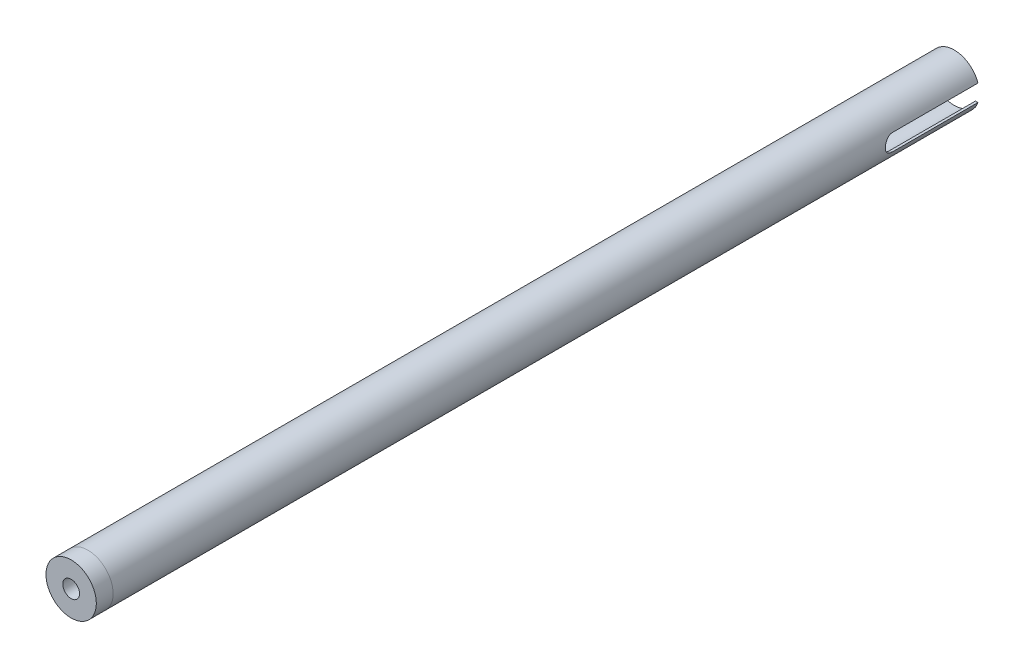
SolidWorks part; units mm, degrees
material "AISI 4130 Steel, normalized at 870C"
ref_plane "Front Plane" through (0, 0, 0) normal (0, 0, 1) x (1, 0, 0)
ref_plane "Top Plane" through (0, 0, 0) normal (0, 1, 0) x (1, 0, 0)
ref_plane "Right Plane" through (0, 0, 0) normal (1, 0, 0) x (0, 0, -1)
sketch "Axis" plane through (0, 0, 0) normal (0, 1, 0) x (1, 0, 0)
  line L0 (0, 0) -> (0, 333.8909) construction
  line L1 (0, 0) -> (0, -21.59) construction
  line L2 (0, 333.8909) -> (-9.525, 333.8909) construction
  line L3 (0, 368.3926) -> (-10.3187, 331.0158) construction
  dimension "D1" = 21.59
  dimension "D2" = 9.525
sketch "Sketch1" plane through (0, 0, 0) normal (0, 0, 1) x (1, 0, 0)
  line L0 (-9.525, 0) -> (9.525, 0) construction
  line L1 (-8.9803, 3.175) -> (8.9803, 3.175)
  line L2 (-8.9803, -3.175) -> (8.9803, -3.175)
  circle A0 centre (0, 0) radius 9.525
  circle A1 centre (0, 0) radius 8.636
  circle A2 centre (0, 0) radius 3.175
  dimension "D1" = 19.05
  dimension "D3" = 6.35
  dimension "D2" = 0.889
  dimension "D4" = 6.35
extrude "Threaded insert 1-1" add sketch "Sketch1" against normal blind 6.35 contours A2 L1 A1 | A1 L1 A0 | A2 L0 A1 L1 | A1 L0 A0 L1 | L0 A1 L2 A0 | L0 A2 L2 A1 | A2 L2 A1 | A1 L2 A0 | L0 A1 L2 A2 | L0 A0 L2 A1 | A0 L0 A1 L1 | A1 L0 A2 L1 region at (5.4259, 1.6615, 0) region at (5.4259, -1.6615, 0) region at (8.8881, 1.6046, 0) region at (8.8881, -1.6046, 0) region at (-5.4259, -1.6615, 0) region at (-5.4259, 1.6615, 0) region at (0, 5.4321, 0) region at (0, -5.4321, 0) region at (0, 8.8265, 0) region at (8.5057, -3.3655, 0) region at (-8.8881, -1.6046, 0) region at (-8.8881, 1.6046, 0)
extrude "Threaded insert 1-2" add sketch "Sketch1<3>" against normal blind 6.35 from surface contours A2 L1 A1 | A2 L0 A1 L1 | L0 A2 L2 A1 | A2 L2 A1 | L0 A1 L2 A2 | A1 L0 A2 L1 region at (5.4259, 1.6615, 0) region at (5.4259, -1.6615, 0) region at (-5.4259, -1.6615, 0) region at (-5.4259, 1.6615, 0) region at (0, 5.4321, 0) region at (0, -5.4321, 0) starting at face at (9.525, 0, -6.35)
sketch "Sketch1<3>" plane through (0, 0, 0) normal (0, 0, 1) x (1, 0, 0) same geometry as "Sketch1"
extrude "A-arm tube" add sketch "Sketch1<4>" against normal up to vertex (333.8909 mm away) from surface separate body contours A1 L1 A0 | A1 L0 A0 L1 | L0 A1 L2 A0 | A1 L2 A0 | L0 A0 L2 A1 | A0 L0 A1 L1 region at (8.8881, 1.6046, 0) region at (8.8881, -1.6046, 0) region at (0, 8.8265, 0) region at (8.5057, -3.3655, 0) region at (-8.8881, -1.6046, 0) region at (-8.8881, 1.6046, 0) up to point (0, 0, -333.8909) starting at face at (8.636, 0, -6.35)
sketch "Sketch1<4>" plane through (0, 0, 0) normal (0, 0, 1) x (1, 0, 0) same geometry as "Sketch1"
extrude "Apex slot" cut sketch "Sketch1<5>" along normal blind 35.56 from surface contours A0 L0 A1 L1 | L0 A0 L2 A1 | A1 L0 A0 L1 | L0 A1 L2 A0 region at (8.8881, 1.6046, 0) region at (8.8881, -1.6046, 0) region at (-8.8881, -1.6046, 0) region at (-8.8881, 1.6046, 0) starting at face at (8.636, 0, -333.8909)
sketch "Sketch1<5>" plane through (0, 0, 0) normal (0, 0, 1) x (1, 0, 0) same geometry as "Sketch1"
fillet "Fillet1" radius 3.175 4 edges at (-8.5057, 3.175, -298.3309) (-8.5057, -3.175, -298.3309) (8.5057, -3.175, -298.3309) (8.5057, 3.175, -298.3309)
equation "\"tube diameter\"= 3 / 4"
equation "\"tube thickness\"= .035"
equation "\"apex thickness\"= .25"
equation "\"tube slot\"= 1.4"
equation "\"D1@Sketch1\"=\"tube diameter\""
equation "\"D2@Sketch1\"=\"tube thickness\""
equation "\"threaded insert hole\" = 1 / 4"
equation "\"D3@Sketch1\"=\"threaded insert hole\""
equation "\"D4@Sketch1\"=\"apex thickness\""
equation "\"D1@Apex slot\" = \"tube slot\""
equation "\"D1@Fillet1\"=\"apex thickness\"/2"
equation "\"D2@Axis\"=\"tube diameter\"/2"
